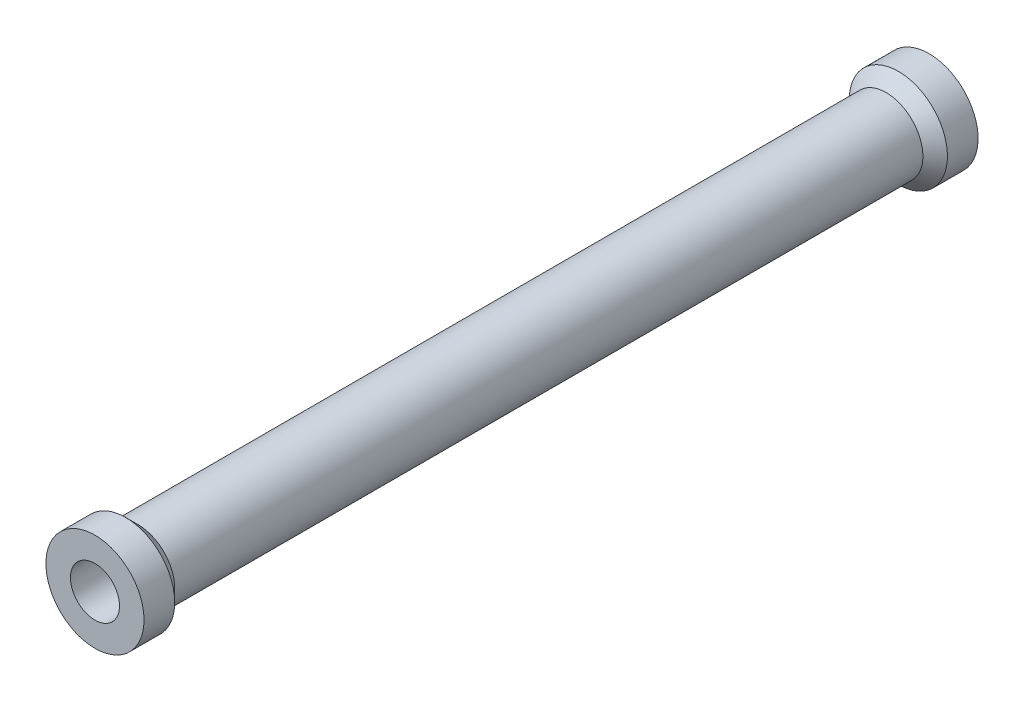
SolidWorks part; units mm, degrees
ref_plane "Front Plane" through (0, 0, 0) normal (0, 0, 1) x (1, 0, 0)
ref_plane "Top Plane" through (0, 0, 0) normal (0, 1, 0) x (1, 0, 0)
ref_plane "Right Plane" through (0, 0, 0) normal (1, 0, 0) x (0, 0, -1)
sketch "Sketch1" plane through (0, 0, 0) normal (0, 0, 1) x (1, 0, 0)
  circle A0 centre (0, 0) radius 4.7625
  dimension "D1" = 9.525
extrude "Boss-Extrude1" add sketch "Sketch1" along normal blind 47.625
sketch "Sketch2" plane through (0, 0, 47.625) normal (0, 0, 1) x (1, 0, 0)
  circle A0 centre (0, 0) radius 6.35
extrude "Boss-Extrude2" add sketch "Sketch2" along normal blind 6.35
chamfer "Chamfer1" distance 2.38 angle 45 1 edges at (6.35, 0, 47.625)
sketch "Sketch3" plane through (0, 0, 53.975) normal (0, 0, 1) x (1, 0, 0)
  circle A0 centre (0, 0) radius 3.175
extrude "Cut-Extrude1" cut sketch "Sketch3" against normal blind 12.7
sketch "Sketch4" plane through (0, 0, 0) normal (0, 0, -1) x (-1, 0, 0)
  circle A0 centre (0, 0) radius 4.7625
extrude "Boss-Extrude3" add sketch "Sketch4" along normal blind 47.625
sketch "Sketch5" plane through (0, 0, -47.625) normal (0, 0, -1) x (-1, 0, 0)
  circle A0 centre (0, 0) radius 6.35
extrude "Boss-Extrude4" add sketch "Sketch5" along normal blind 6.35
chamfer "Chamfer2" distance 2.38 angle 45 1 edges at (-6.35, 0, -47.625)
sketch "Sketch6" plane through (0, 0, -53.975) normal (0, 0, -1) x (-1, 0, 0)
  circle A0 centre (0, 0) radius 3.175
extrude "Cut-Extrude2" cut sketch "Sketch6" against normal blind 12.7
sketch "Sketch7" plane through (0, 0, -53.975) normal (0, 0, -1) x (-1, 0, 0)
  point P0 (0, 0)
